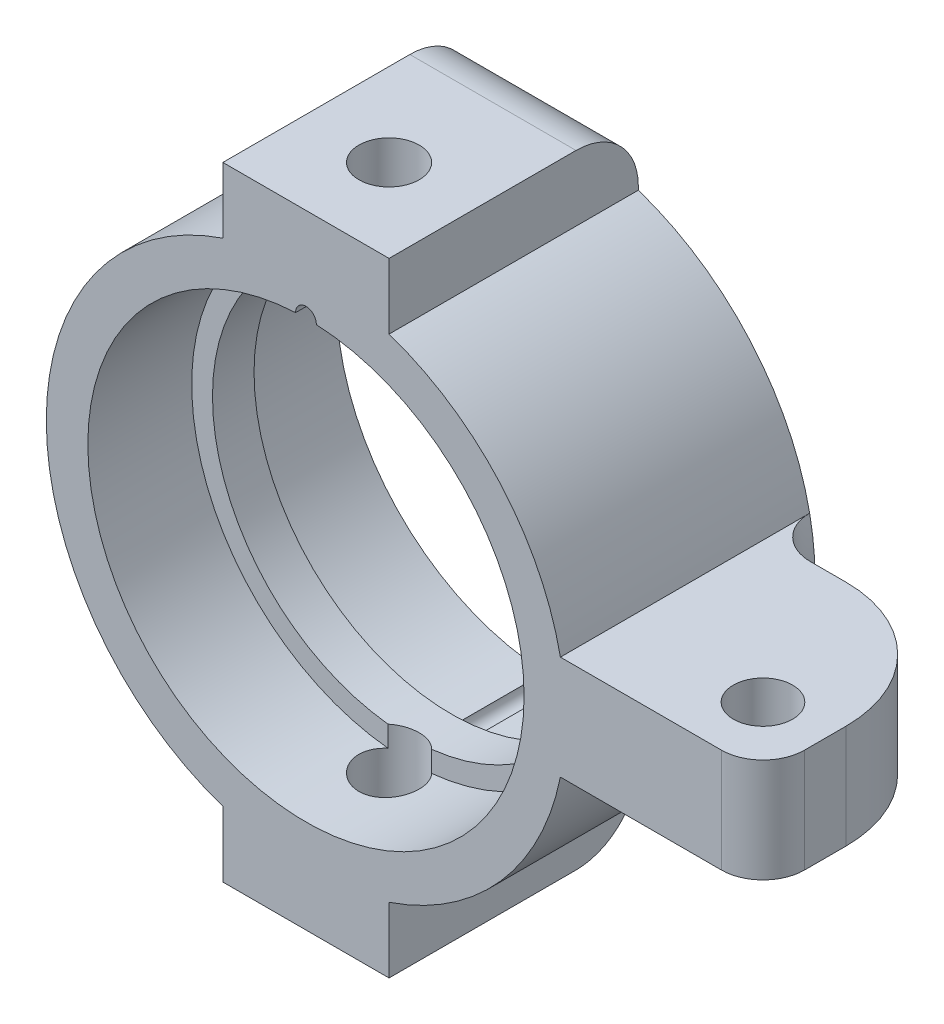
SolidWorks part; units mm, degrees
ref_plane "Front Plane" through (0, 0, 0) normal (0, 0, 1) x (1, 0, 0)
ref_plane "Top Plane" through (0, 0, 0) normal (0, 1, 0) x (1, 0, 0)
ref_plane "Right Plane" through (0, 0, 0) normal (1, 0, 0) x (0, 0, -1)
sketch "Sketch1" plane through (0, 0, 0) normal (0, 0, 1) x (1, 0, 0)
  circle A0 centre (0, 0) radius 9.5
  circle A1 centre (0, 0) radius 12.5
  dimension "D1" = 19
  dimension "D2" = 3
extrude "Boss-Extrude1" add sketch "Sketch1" along normal blind 7
sketch "Sketch2" plane through (0, 0, 7) normal (0, 0, 1) x (1, 0, 0)
  circle A0 centre (0, 0) radius 9.5
  circle A1 centre (0, 0) radius 12.5
  circle A2 centre (0, 0) radius 12.5
  dimension "D2" = 19
  dimension "D1" = 0
extrude "Boss-Extrude2" add sketch "Sketch2" along normal blind 5
sketch "Sketch3" plane through (0, 0, 0) normal (0, 1, 0) x (1, 0, 0)
  line L4 (12.5, 0) -> (-12.5, 0) construction
  line L5 (-4, 0) -> (4, 0)
  line L6 (-4, 0) -> (-4, -12)
  line L7 (-4, -12) -> (4, -12)
  line L8 (4, 0) -> (4, -12)
  line L9 (-12.5, -12) -> (12.5, -12) construction
  point P8 (0, 0)
  dimension "D1" = 8
extrude "Boss-Extrude3" add sketch "Sketch3" along normal blind 15 and the other way blind 15
sketch "Sketch4" plane through (0, 0, 12) normal (0, 0, 1) x (1, 0, 0)
  circle A0 centre (0, 0) radius 9.5
  dimension "D1" = 19
fillet "Fillet1" radius 3 2 edges at (0, -15, 0) (0, 15, 0)
sketch "Sketch6" plane through (0, 15, 0) normal (0, 1, 0) x (1, 0, 0)
  line L0 (-4, -12) -> (4, -12) construction
  circle A0 centre (0, -8) radius 1.45
  dimension "D1" = 4
  dimension "D2" = 2.9
extrude "Cut-Extrude3" cut sketch "Sketch6" against normal through all
sketch "Sketch7" plane through (4, 0, 0) normal (1, 0, 0) x (0, 0, -1)
  line L0 (-12, 9.5) -> (-12, -9.5) construction
  line L1 (-12, -2.5) -> (-2, -2.5)
  line L2 (-12, -2.5) -> (-12, 2.5)
  line L3 (-12, 2.5) -> (-2, 2.5)
  line L4 (-2, -2.5) -> (-2, 2.5)
  point P6 (-12, 0)
  dimension "D1" = 5
  dimension "D2" = 10
extrude "Boss-Extrude4" add sketch "Sketch7" along normal blind 18
sketch "Sketch11" plane through (0, 0, 0) normal (0, 0, -1) x (-1, 0, 0)
sketch "Sketch12" plane through (0, 0, 0) normal (0, 0, -1) x (-1, 0, 0)
  circle A0 centre (0, 0) radius 10.525
  dimension "D1" = 21.05
extrude "Cut-Extrude7" cut sketch "Sketch12" against normal blind 5
sketch "Sketch13" plane through (0, 0, 12) normal (0, 0, 1) x (1, 0, 0)
extrude "Cut-Extrude8" cut sketch "Sketch4" against normal through all
sketch "Sketch14" plane through (0, 0, 0) normal (0, 0, -1) x (-1, 0, 0)
  circle A0 centre (0, 10.525) radius 0.5
  circle A1 centre (0, 0) radius 10.525 construction
  circle A2 centre (0, 0) radius 10.525 construction
  circle A3 centre (0, -10.525) radius 0.5
  dimension "D1" = 1
extrude "Cut-Extrude9" cut sketch "Sketch14" against normal blind 5
sketch "Sketch15" plane through (0, 0, 12) normal (0, 0, 1) x (1, 0, 0)
  circle A0 centre (0, 0) radius 10.5
  circle A1 centre (0, 10.5) radius 0.5
  circle M2 centre (0, 0) radius 9.5
  dimension "D1" = 21
  dimension "D2" = 1
extrude "Cut-Extrude10" cut sketch "Sketch15" against normal blind 5 contours M2 | A1 A0 M2 | A0 A1 | A0 A1 region at (-7.0409, -7.3844, 12) region at (0, 10.2857, 12) region at (0, 10.71, 12) region at (0, 0, 12)
sketch "Sketch16" plane through (0, 2.5, 0) normal (0, 1, 0) x (1, 0, 0)
  line L1 (22, -12) -> (12.2474, -12) construction
  line L2 (22, -2) -> (22, -12) construction
  circle A0 centre (19, -9) radius 1.425
  dimension "D1" = 2.85
  dimension "D2" = 3
  dimension "D3" = 3
extrude "Cut-Extrude11" cut sketch "Sketch16" against normal blind 10
fillet "Fillet2" radius 6 1 edges at (22, 0, 2)
fillet "Fillet4" radius 2 1 edges at (22, 0, 12)
fillet "Fillet5" radius 2 1 edges at (12.5, 0, 2)
